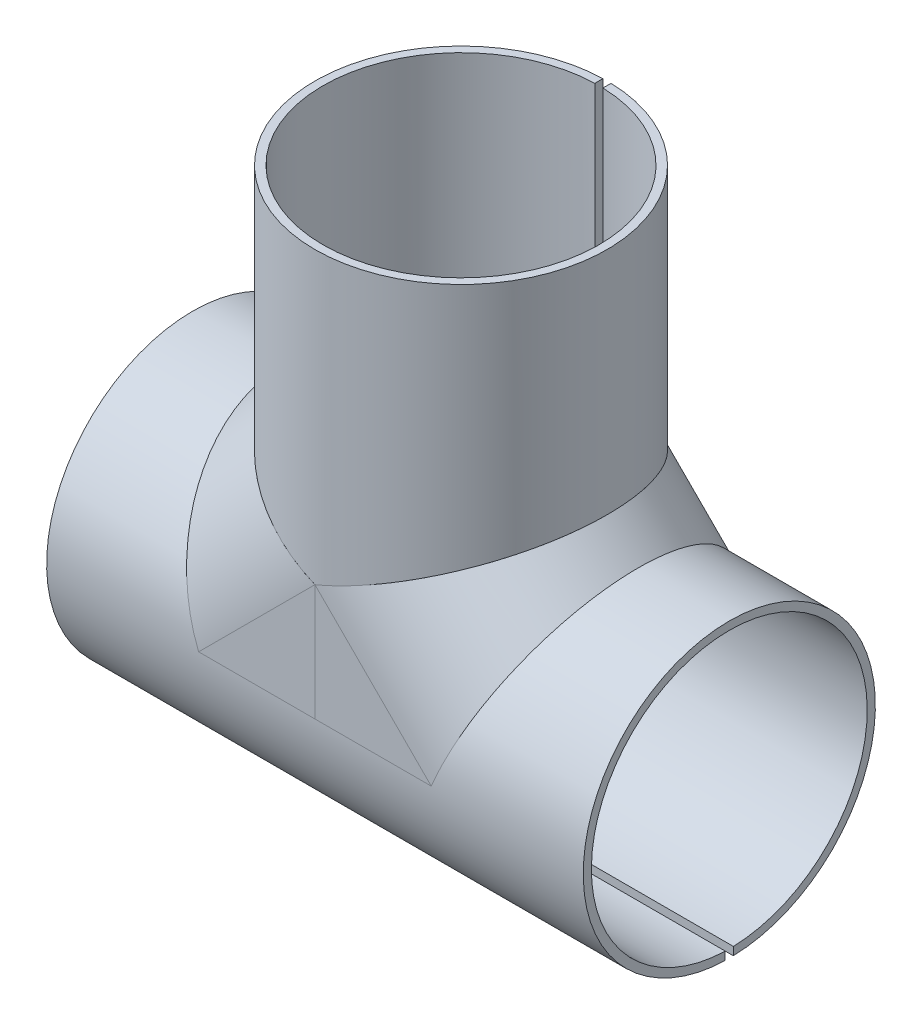
SolidWorks part; units mm, degrees
ref_plane "前视基准面" through (0, 0, 0) normal (0, 0, 1) x (1, 0, 0)
ref_plane "上视基准面" through (0, 0, 0) normal (0, 1, 0) x (1, 0, 0)
ref_plane "右视基准面" through (0, 0, 0) normal (1, 0, 0) x (0, 0, -1)
sketch "草图1" plane through (0, 0, 0) normal (0, 0, 1) x (1, 0, 0)
  line L0 (0, 50) -> (0, 0) construction
  line L1 (-33, 0) -> (33, 0) construction
  line L2 (-17.963, 50) -> (17.963, 50) construction
  line L3 (33, 17.963) -> (33, -17.963) construction
  line L4 (17.963, 50) -> (17.963, 21.7467) construction
  line L5 (17.963, 21.7467) -> (21.7467, 17.963) construction
  line L6 (21.7467, 17.963) -> (33, 17.963) construction
  line L7 (21.7467, 17.963) -> (14.3062, 0) construction
  line L8 (0, 14.3062) -> (-14.3062, 0) construction
  line L9 (17.963, 21.7467) -> (0, 14.3062) construction
  line L10 (7.1531, 7.1531) -> (19.8549, 19.8549) construction
  line L11 (-17.963, 50) -> (-17.963, 21.7467) construction
  line L12 (-17.963, 21.7467) -> (-21.7467, 17.963) construction
  line L13 (-21.7467, 17.963) -> (-33, 17.963) construction
  line L14 (-33, 17.963) -> (-33, -17.963) construction
  line L15 (0, 14.3062) -> (-17.963, 21.7467) construction
  line L16 (14.3062, 0) -> (0, 14.3062) construction
  line L17 (-14.3062, 0) -> (-21.7467, 17.963) construction
  line L18 (17.963, 21.7467) -> (-17.963, 21.7467) construction
  line L19 (0, 50) -> (17.963, 50) construction
  line L20 (0, 14.3062) -> (0, 21.7467) construction
  line L21 (0, 0) -> (0, -1) construction
  line L22 (0, 0) -> (0, 50)
  dimension "D1" = 45
  dimension "L3" = 66
  dimension "L1" = 50
  dimension "R" = 17.963
  dimension "L2" = 14.3062
  dimension "t" = 1
sketch "草图2" plane through (0, 0, 0) normal (0, 1, 0) x (1, 0, 0)
  line L0 (0, 17.963) -> (0, -17.963) construction
  circle A0 centre (0, 0) radius 17.963
extrude "拉伸-薄壁1" add sketch "草图2" along normal up to vertex (50 mm away) thin up to point (0, 50, 0) thin type one direction reverse wall 1
sketch "草图3" plane through (0, 0, 0) normal (1, 0, 0) x (0, 0, -1)
  circle A0 centre (0, 0) radius 17.963
extrude "拉伸-薄壁2" add sketch "草图3" along normal up to vertex (33 mm away) and the other way up to vertex (33 mm away) separate body thin up to point (33, 0, 0) other way up to point (-33, 17.963, 0) thin type one direction reverse wall 1
ref_plane "基准面1" through (0, 14.3062, 0) normal (-0.7071, 0.7071, 0) x (0, 0, 1)
ref_plane "基准面2" through (0, 14.3062, 0) normal (-0.7071, -0.7071, 0) x (0, 0, 1)
sketch "草图4" plane through (0, 14.3062, 0) normal (-0.7071, 0.7071, 0) x (0, 0, 1)
  circle A0 centre (0, 0) radius 17.963
extrude "拉伸-薄壁3" add sketch "草图4" against normal up to vertex (20.232 mm away) separate body thin up to point (14.3062, 0, 0) thin type one direction reverse wall 1
sketch "草图8" plane through (0, 0, 0) normal (0, 0, 1) x (1, 0, 0)
  line L0 (17.963, 21.7467) -> (0, 14.3062) construction
  line L1 (14.3062, 0) -> (0, 14.3062) construction
  line L2 (21.7467, 17.963) -> (14.3062, 0) construction
  line L3 (17.963, 21.7467) -> (21.7467, 17.963) construction
  line L4 (17.963, 21.7467) -> (0, 14.3062)
  line L5 (14.3062, 0) -> (0, 14.3062)
  line L6 (21.7467, 17.963) -> (14.3062, 0)
  line L7 (17.963, 21.7467) -> (21.7467, 17.963)
extrude "切除-拉伸2" cut sketch "草图8" against normal through all and the other way through all flip side to cut
sketch "草图5" plane through (0, 14.3062, 0) normal (-0.7071, -0.7071, 0) x (0, 0, 1)
  circle A0 centre (0, 0) radius 17.963
extrude "拉伸-薄壁4" add sketch "草图5" along normal up to vertex (20.232 mm away) separate body thin up to point (-14.3062, 0, 0) thin type one direction reverse wall 1
sketch "草图9" plane through (0, 0, 0) normal (0, 0, 1) x (1, 0, 0)
  line L0 (0, 14.3062) -> (-17.963, 21.7467) construction
  line L1 (-14.3062, 0) -> (-21.7467, 17.963) construction
  line L2 (0, 14.3062) -> (-14.3062, 0) construction
  line L3 (-17.963, 21.7467) -> (-21.7467, 17.963) construction
  line L4 (0, 14.3062) -> (-17.963, 21.7467)
  line L5 (-14.3062, 0) -> (-21.7467, 17.963)
  line L6 (0, 14.3062) -> (-14.3062, 0)
  line L7 (-17.963, 21.7467) -> (-21.7467, 17.963)
extrude "切除-拉伸3" cut sketch "草图9" against normal through all and the other way through all flip side to cut
ref_plane "基准面3" through (0, 0, 17.963) normal (0, 0, 1) x (1, 0, 0)
sketch "草图7" plane through (0, 0, 17.963) normal (0, 0, 1) x (1, 0, 0)
  line L1 (0, 14.3062) -> (-14.3062, 0)
  line L2 (-14.3062, 0) -> (0, 0)
  line L3 (0, 0) -> (0, 14.3062)
extrude "凸台-拉伸1" add sketch "草图7" against normal blind 1
sketch "草图10" plane through (0, 0, 17.963) normal (0, 0, 1) x (1, 0, 0)
  line L0 (0, 14.3062) -> (0, 0)
  line L1 (0, 0) -> (14.3062, 0)
  line L2 (14.3062, 0) -> (0, 14.3062)
extrude "凸台-拉伸2" add sketch "草图10" against normal blind 1
mirror "镜向1" about plane through (0, 0, 0) normal (0, 0, 1) of "凸台-拉伸1"
mirror "镜向2" about plane through (0, 0, 0) normal (0, 0, 1) of "凸台-拉伸2"
sketch "草图6" plane through (0, 0, 0) normal (0, 0, 1) x (1, 0, 0)
  line L0 (-17.963, 21.7467) -> (0, 14.3062)
  line L1 (0, 14.3062) -> (17.963, 21.7467)
  line L3 (17.963, 21.7467) -> (17.963, 50)
  line L4 (17.963, 50) -> (-17.963, 50)
  line L5 (-17.963, 50) -> (-17.963, 21.7467)
extrude "切除-拉伸1" cut sketch "草图6" against normal through all and the other way through all flip side to cut
sketch "草图11" plane through (0, 0, 0) normal (0, 0, 1) x (1, 0, 0)
  line L0 (-14.3062, 0) -> (-21.7467, 17.963) construction
  line L1 (21.7467, 17.963) -> (14.3062, 0) construction
  line L2 (-14.3062, 0) -> (-21.7467, 17.963)
  line L3 (21.7467, 17.963) -> (14.3062, 0)
  line L4 (-14.3062, 0) -> (14.3062, 0)
  line L5 (-21.7467, 17.963) -> (21.7467, 17.963)
extrude "切除-拉伸4" cut sketch "草图11" against normal through all and the other way through all
sketch "草图12" plane through (0, 0, 0) normal (0, 1, 0) x (1, 0, 0)
  line L0 (-33, 0) -> (33, 0)
extrude "切除-拉伸-薄壁1" cut sketch "草图12" against normal through all thin thin type mid plane wall 1
extrude "切除-拉伸-薄壁2" cut sketch "草图1" against normal through all thin thin type mid plane wall 1
equation "\"D5@拉伸-薄壁1\" = \"t@草图1\""
equation "\"D5@拉伸-薄壁2\" = \"t@草图1\""
equation "\"D5@拉伸-薄壁3\" = \"t@草图1\""
equation "\"D5@拉伸-薄壁4\" = \"t@草图1\""
equation "\"D1@凸台-拉伸1\" = \"t@草图1\""
equation "\"D1@凸台-拉伸2\" = \"t@草图1\""
